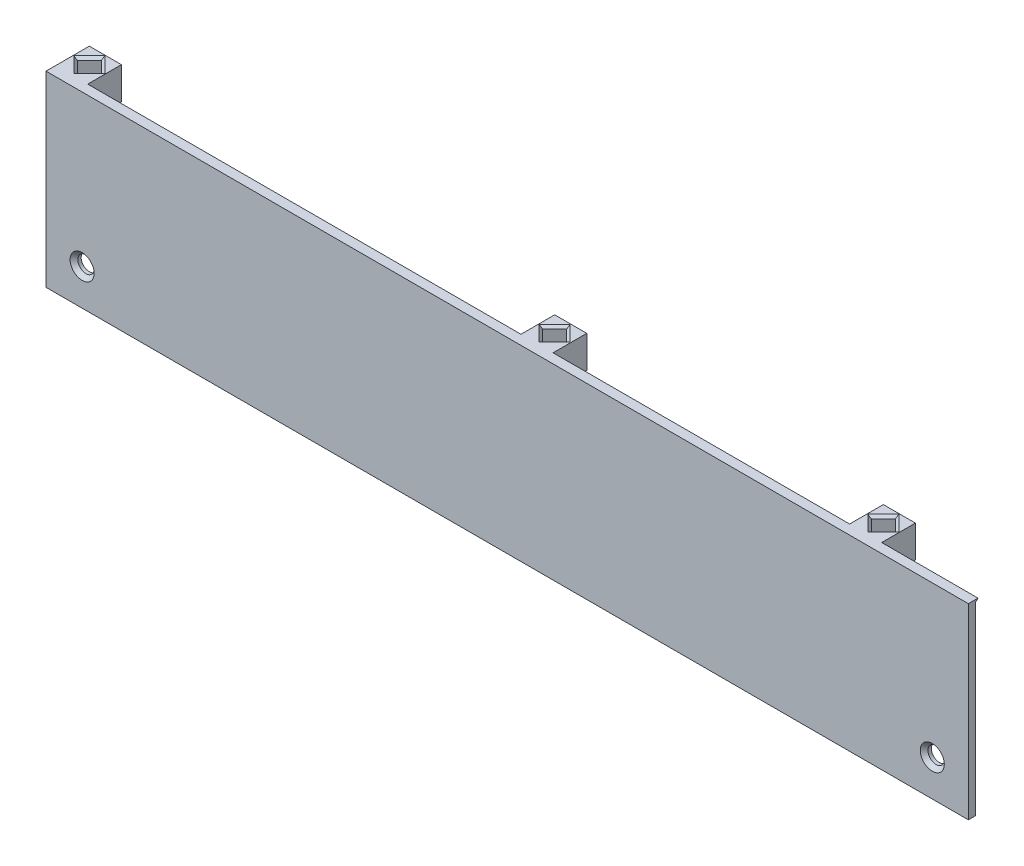
SolidWorks part; units mm, degrees
ref_plane "Front Plane" through (0, 0, 0) normal (0, 0, 1) x (1, 0, 0)
ref_plane "Top Plane" through (0, 0, 0) normal (0, 1, 0) x (1, 0, 0)
ref_plane "Right Plane" through (0, 0, 0) normal (1, 0, 0) x (0, 0, -1)
sketch "Sketch1" plane through (0, 0, 0) normal (0, 0, 1) x (1, 0, 0)
  line L1 (0, 0) -> (243.332, 0)
  line L2 (0, 0) -> (0, 49.395)
  line L3 (0, 49.395) -> (243.332, 49.395)
  line L4 (243.332, 0) -> (243.332, 49.395)
  dimension "D1" = 49.395
  dimension "D2" = 243.332
extrude "Boss-Extrude1" add sketch "Sketch1" along normal blind 1.905
sketch "Sketch2" plane through (0, 0, 0) normal (0, 0, 1) x (1, 0, 0)
  line L0 (243.332, 49.395) -> (0, 49.395) construction
  line L1 (0, 49.395) -> (8.4667, 49.395)
  line L2 (0, 49.395) -> (0, 40.9283)
  line L3 (0, 40.9283) -> (8.4667, 40.9283)
  line L4 (8.4667, 49.395) -> (8.4667, 40.9283)
  line L5 (122.7667, 49.395) -> (131.2333, 49.395)
  line L6 (122.7667, 49.395) -> (122.7667, 40.9283)
  line L7 (122.7667, 40.9283) -> (131.2333, 40.9283)
  line L8 (131.2333, 49.395) -> (131.2333, 40.9283)
  line L9 (243.332, 0) -> (243.332, 49.395) construction
  line L10 (209.4653, 49.395) -> (217.932, 49.395)
  line L11 (209.4653, 49.395) -> (209.4653, 40.9283)
  line L12 (209.4653, 40.9283) -> (217.932, 40.9283)
  line L13 (217.932, 49.395) -> (217.932, 40.9283)
  dimension "D1" = 25.4
  dimension "D2" = 114.3
  dimension "D4" = 8.4667
extrude "Boss-Extrude2" add sketch "Sketch2" against normal blind 9.525
sketch "Sketch3" plane through (0, 49.395, 0) normal (0, 1, 0) x (1, 0, 0)
  line L0 (1.0583, 5.2917) -> (4.2333, 8.4667)
  line L1 (1.0583, 5.2917) -> (4.2333, 2.1167)
  line L2 (4.2333, 8.4667) -> (7.4083, 5.2917)
  line L3 (4.2333, 2.1167) -> (7.4083, 5.2917)
  line L4 (1.0583, 5.2917) -> (7.4083, 5.2917) construction
  line L5 (4.2333, 8.4667) -> (4.2333, 2.1167) construction
  line L6 (123.825, 5.2917) -> (127, 8.4667)
  line L7 (123.825, 5.2917) -> (127, 2.1167)
  line L8 (127, 8.4667) -> (130.175, 5.2917)
  line L9 (127, 2.1167) -> (130.175, 5.2917)
  line L10 (123.825, 5.2917) -> (130.175, 5.2917) construction
  line L11 (127, 8.4667) -> (127, 2.1167) construction
  line L12 (210.5237, 5.2917) -> (213.6987, 8.4667)
  line L13 (210.5237, 5.2917) -> (213.6987, 2.1167)
  line L14 (213.6987, 8.4667) -> (216.8737, 5.2917)
  line L15 (213.6987, 2.1167) -> (216.8737, 5.2917)
  line L16 (210.5237, 5.2917) -> (216.8737, 5.2917) construction
  line L17 (213.6987, 8.4667) -> (213.6987, 2.1167) construction
  line L18 (8.4667, 9.525) -> (0, 9.525) construction
  line L19 (131.2333, 9.525) -> (122.7667, 9.525) construction
  line L20 (217.932, 9.525) -> (209.4653, 9.525) construction
  line L21 (8.4667, 9.525) -> (0, 9.525) construction
  point P1 (4.2333, 5.2917)
  point P2 (127, 5.2917)
  point P3 (213.6987, 5.2917)
  point P13 (4.2333, 9.525)
  point P20 (127, 9.525)
  point P23 (213.6987, 9.525)
  dimension "D1" = 6.35
  dimension "D2" = 4.2333
extrude "Cut-Extrude1" cut sketch "Sketch3" against normal blind 6.35
chamfer "Chamfer1" distance 0.635 angle 45 24 edges at (212.1112, 43.045, -6.8792) (215.2862, 43.045, -6.8792) (215.2862, 43.045, -3.7042) (212.1112, 43.045, -3.7042) (2.6458, 43.045, -6.8792) (5.8208, 43.045, -6.8792) (5.8208, 43.045, -3.7042) (2.6458, 43.045, -3.7042) (125.4125, 43.045, -6.8792) (128.5875, 43.045, -6.8792) (128.5875, 43.045, -3.7042) (125.4125, 43.045, -3.7042) (212.1112, 49.395, -6.8792) (212.1112, 49.395, -3.7042) (215.2862, 49.395, -6.8792) (215.2862, 49.395, -3.7042) (2.6458, 49.395, -6.8792) (2.6458, 49.395, -3.7042) (5.8208, 49.395, -6.8792) (5.8208, 49.395, -3.7042) (128.5875, 49.395, -3.7042) (128.5875, 49.395, -6.8792) (125.4125, 49.395, -6.8792) (125.4125, 49.395, -3.7042)
sketch "Sketch4" plane through (243.332, 0, 0) normal (1, 0, 0) x (0, 0, -1)
  line L0 (0, 49.395) -> (0.635, 49.395)
  line L1 (9.525, 49.395) -> (0, 49.395) construction
  line L2 (0.635, 49.395) -> (0, 48.76)
  line L3 (0, 0) -> (0, 49.395) construction
  line L4 (0, 48.76) -> (0, 49.395)
  dimension "D1" = 0.635
extrude "Boss-Extrude3" add sketch "Sketch4" against normal up to surface (243.332 mm away) up to face at (0, 30.1078, -2.54)
sketch "Sketch5" plane through (0, 0, 1.905) normal (0, 0, 1) x (1, 0, 0)
  line L0 (0, 9.525) -> (9.525, 9.525) construction
  line L1 (9.525, 9.525) -> (9.525, 0) construction
  line L2 (0, 0) -> (243.332, 0) construction
  line L3 (243.332, 9.525) -> (233.807, 9.525) construction
  line L4 (243.332, 0) -> (243.332, 49.395) construction
  line L5 (233.807, 9.525) -> (233.807, 0) construction
  line L6 (0, 49.395) -> (0, 0) construction
  point P11 (233.807, 9.525)
  point P15 (9.525, 9.525)
  dimension "D1" = 9.525
hole_wizard "#6 Clearance Hole1" positions "Sketch5" profile "Sketch6" hole size "#6" standard "ANSI Inch" end condition through all
sketch "Sketch6" plane through (9.525, 9.525, 1.905) normal (1, 0, 0) x (0, -1, 0)
  line L0 (0, 0) -> (0, 11.43)
  line L1 (0, 11.43) -> (2.1526, 11.43)
  line L2 (2.1526, 11.43) -> (2.1526, 1.0224)
  line L3 (2.1526, 1.0224) -> (3.175, 0)
  line L5 (3.175, 0) -> (0, 0)
  line L6 (-2.1526, 1.0224) -> (-3.175, 0) construction
  line L11 (0, -6.35) -> (0, 107.95) construction
  dimension "Thru Hole Dia." = 4.3053
  dimension "Thru Hole Depth" = 11.43
  dimension "Near C'Sink Dia." = 6.35
  dimension "Near C'Sink Angle" = 90
